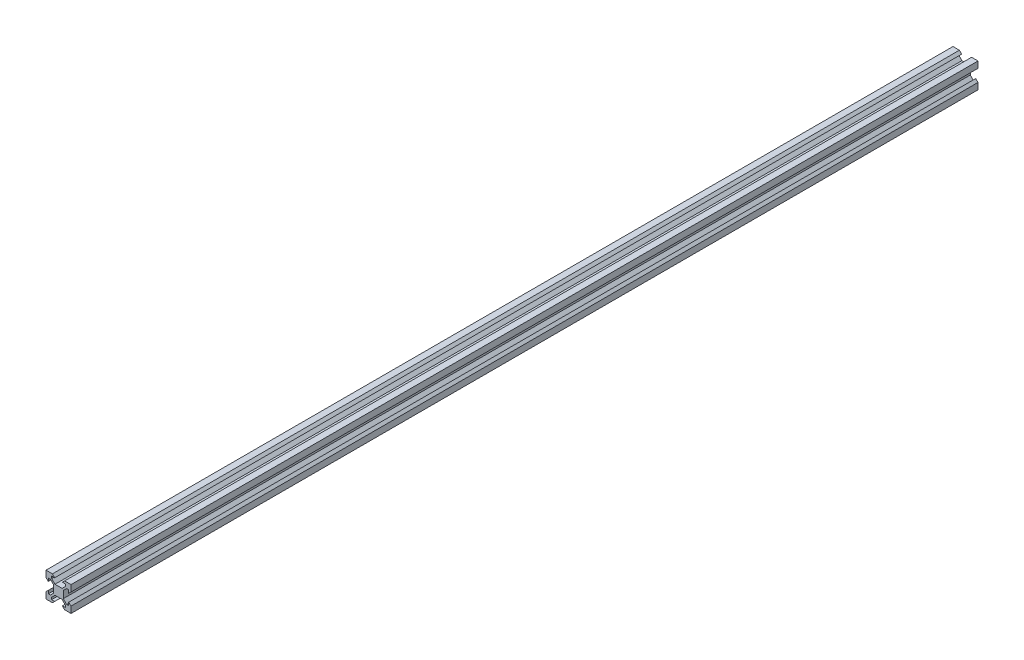
SolidWorks part; units mm, degrees
ref_plane "Front Plane" through (0, 0, 0) normal (0, 0, 1) x (1, 0, 0)
ref_plane "Top Plane" through (0, 0, 0) normal (0, 1, 0) x (1, 0, 0)
ref_plane "Right Plane" through (0, 0, 0) normal (1, 0, 0) x (0, 0, -1)
sketch "Sketch1" plane through (0, 0, 0) normal (0, 0, 1) x (1, 0, 0)
  line L1 (0, 0) -> (20, 0)
  line L2 (0, 0) -> (0, 20)
  line L3 (0, 20) -> (20, 20)
  line L4 (20, 0) -> (20, 20)
  line L5 (0, 0) -> (20, 20) construction
  line L6 (0, 20) -> (20, 0) construction
  point P4 (10, 10)
  dimension "D1" = 20
  dimension "D2" = 20
extrude "Boss-Extrude1" add sketch "Sketch1" along normal blind 725
sketch "Sketch2" plane through (0, 0, 725) normal (0, 0, 1) x (1, 0, 0)
  line L4 (0, 0) -> (20, 20) construction
  line L5 (4.5, 18.18) -> (6.94, 18.18)
  line L6 (4.5, 16.4758) -> (4.5, 18.18)
  line L15 (7.1658, 13.81) -> (4.5, 16.4758)
  line L17 (12.8342, 13.81) -> (7.1658, 13.81)
  line L27 (15.5, 16.4758) -> (12.8342, 13.81)
  line L29 (15.5, 18.18) -> (15.5, 16.4758)
  line L31 (13.06, 18.18) -> (15.5, 18.18)
  line L33 (14.88, 20) -> (5.12, 20)
  line L35 (6.94, 18.18) -> (5.12, 20)
  line L54 (14.88, 20) -> (13.06, 18.18)
  line L56 (14.88, 0) -> (13.06, 1.82)
  line L57 (6.94, 1.82) -> (5.12, 0)
  line L58 (14.88, 0) -> (5.12, 0)
  line L68 (13.06, 1.82) -> (15.5, 1.82)
  line L71 (15.5, 1.82) -> (15.5, 3.5242)
  line L81 (15.5, 3.5242) -> (12.8342, 6.19)
  line L82 (12.8342, 6.19) -> (7.1658, 6.19)
  line L83 (7.1658, 6.19) -> (4.5, 3.5242)
  line L84 (4.5, 3.5242) -> (4.5, 1.82)
  line L85 (4.5, 1.82) -> (6.94, 1.82)
  line L136 (20, 0) -> (10, 0) construction
  line L137 (0, 0) -> (20, 0) construction
  line L186 (1.82, 4.5) -> (1.82, 6.94)
  line L187 (3.5242, 4.5) -> (1.82, 4.5)
  line L188 (6.19, 7.1658) -> (3.5242, 4.5)
  line L189 (6.19, 12.8342) -> (6.19, 7.1658)
  line L190 (3.5242, 15.5) -> (6.19, 12.8342)
  line L191 (1.82, 15.5) -> (3.5242, 15.5)
  line L192 (1.82, 13.06) -> (1.82, 15.5)
  line L193 (0, 14.88) -> (0, 5.12)
  line L194 (1.82, 6.94) -> (0, 5.12)
  line L195 (0, 14.88) -> (1.82, 13.06)
  line L203 (20, 14.88) -> (18.18, 13.06)
  line L205 (18.18, 6.94) -> (20, 5.12)
  line L206 (20, 14.88) -> (20, 5.12)
  line L207 (18.18, 13.06) -> (18.18, 15.5)
  line L208 (18.18, 15.5) -> (16.4758, 15.5)
  line L209 (16.4758, 15.5) -> (13.81, 12.8342)
  line L210 (13.81, 12.8342) -> (13.81, 7.1658)
  line L211 (13.81, 7.1658) -> (16.4758, 4.5)
  line L212 (16.4758, 4.5) -> (18.18, 4.5)
  line L213 (18.18, 4.5) -> (18.18, 6.94)
extrude "Cut-Extrude1" cut sketch "Sketch2" against normal through all
